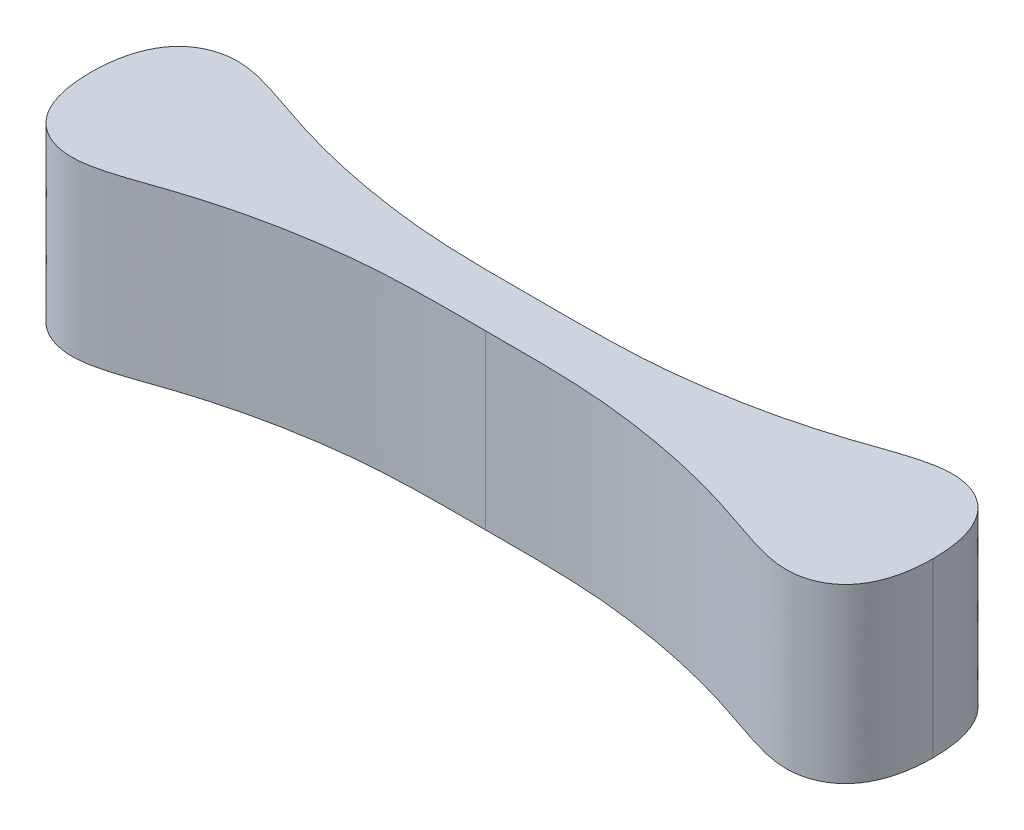
SolidWorks part; units mm, degrees
ref_plane "Front Plane" through (0, 0, 0) normal (0, 0, 1) x (1, 0, 0)
ref_plane "Top Plane" through (0, 0, 0) normal (0, 1, 0) x (1, 0, 0)
ref_plane "Right Plane" through (0, 0, 0) normal (1, 0, 0) x (0, 0, -1)
sketch "Sketch2" plane through (0, 0, 0) normal (0, 1, 0) x (1, 0, 0)
  line L0 (0, 4) -> (0, -4) construction
  line L1 (0, 0) -> (-63.5, 0) construction
  line L2 (3.1171, 4) -> (-3.1171, 4) construction
  line L3 (-63.5, 6.8929) -> (-63.5, -6.8929) construction
  circle A0 centre (0, 0) radius 63.5 construction
  spline S0 degree 3 poles (-63.5, 0) (-63.5, 8.6138) (-58.6666, 12.4018) (-50.8683, 12.6311) (-39.9828, 8.368) (-28.809, 5.7287) (-14.3442, 3.8972) (-5.9297, 4) (0, 4) knots 0 0 0 0 0.199844 0.238289 0.384449 0.645138 0.746282 1 1 1 1
  spline S1 degree 3 poles (-63.5, 0) (-63.5, -8.6138) (-58.6666, -12.4018) (-50.8683, -12.6311) (-39.9828, -8.368) (-28.809, -5.7287) (-14.3442, -3.8972) (-5.9297, -4) (0, -4) knots 0 0 0 0 0.199844 0.238289 0.384449 0.645138 0.746282 1 1 1 1
  spline S2 degree 3 poles (63.5, 0) (63.5, 8.6138) (58.6666, 12.4018) (50.8683, 12.6311) (39.9828, 8.368) (28.809, 5.7287) (14.3442, 3.8972) (5.9297, 4) (0, 4) knots 0 0 0 0 0.199844 0.238289 0.384449 0.645138 0.746282 1 1 1 1
  spline S3 degree 3 poles (63.5, 0) (63.5, -8.6138) (58.6666, -12.4018) (50.8683, -12.6311) (39.9828, -8.368) (28.809, -5.7287) (14.3442, -3.8972) (5.9297, -4) (0, -4) knots 0 0 0 0 0.199844 0.238289 0.384449 0.645138 0.746282 1 1 1 1
  point P4 (-57.9716, 11.2777)
  point P7 (-43.6877, 7.6786)
  point P9 (-21.4183, 6.104)
  point P11 (-11.7457, 4.8669)
  point P14 (-25.0174, 5.3167)
  point P15 (-49.0863, 7.5662)
  point P16 (-55.8346, 16.2265)
  point P17 (-45.0374, 10.4904)
  point P18 (-52.6854, 16.339)
  point P19 (-54.0351, 12.5149)
  point P20 (-42.9111, 9.6943)
  point P21 (0, 0)
  point P24 (0, 0)
  point P40 (-17.9234, 4.4453)
  dimension "D1" = 63.5
  dimension "D2" = 8
extrude "Boss-Extrude1" add sketch "Sketch2" along normal blind 26
